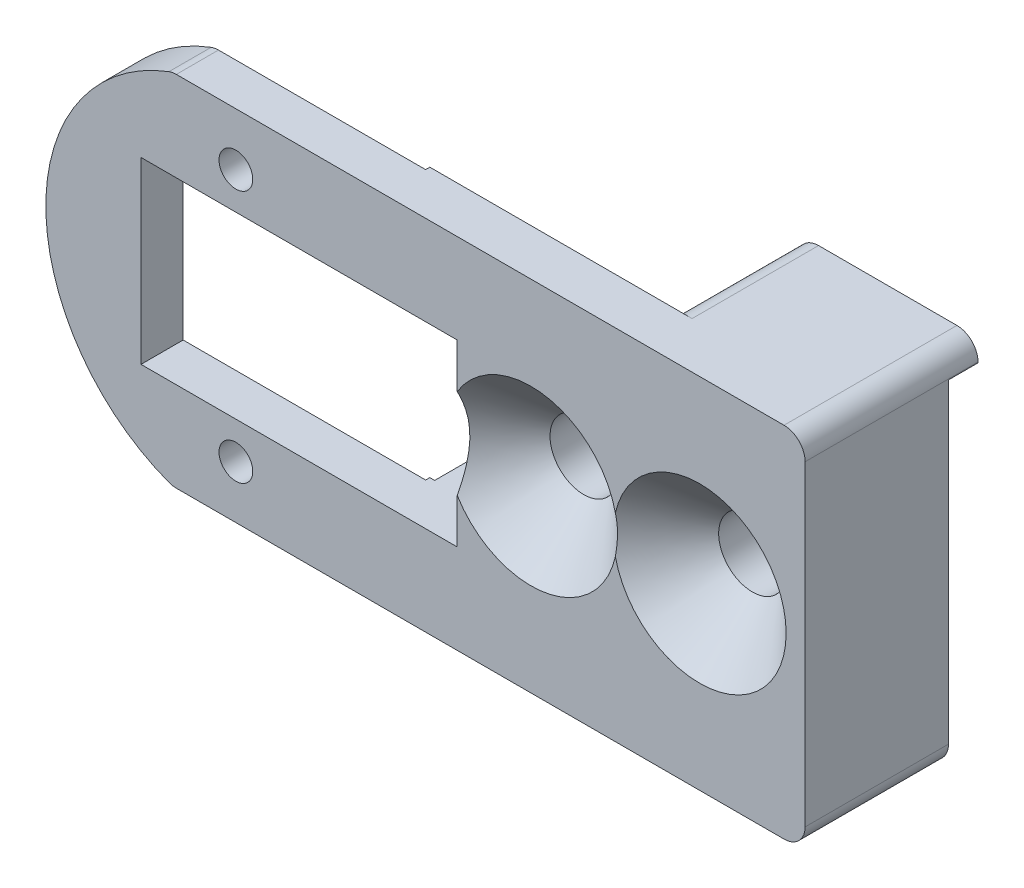
SolidWorks part; units mm, degrees
ref_plane "Front Plane" through (0, 0, 0) normal (0, 0, 1) x (1, 0, 0)
ref_plane "Top Plane" through (0, 0, 0) normal (0, 1, 0) x (1, 0, 0)
ref_plane "Right Plane" through (0, 0, 0) normal (1, 0, 0) x (0, 0, -1)
sketch "Sketch1" plane through (0, 0, 0) normal (0, 0, 1) x (1, 0, 0)
  line L0 (170.9232, 175.5757) -> (267.7046, 169.0678) construction
  line L1 (170.9129, 175.4066) -> (266.125, 169.2097)
  line L2 (268.1688, 170.6248) -> (275.7745, 195.6897)
  line L3 (278.0899, 197.0683) -> (286.8931, 195.2639)
  line L4 (289.2085, 196.6424) -> (291.5751, 204.4416)
  line L5 (289.6612, 207.0223) -> (276.2726, 207.0223)
  line L6 (275.0815, 206.629) -> (256.4226, 192.7962)
  line L7 (255.3092, 192.4043) -> (161.1781, 188.7441)
  line L8 (170.9129, 175.4066) -> (160.0193, 176.7108)
  line L9 (263.8006, 181.4562) -> (263.2585, 179.5311) construction
  line L10 (263.8006, 181.4562) -> (263.2585, 179.5311) construction
  line L11 (264.6293, 181.2229) -> (264.0871, 179.2977) construction
  line L12 (262.972, 181.6896) -> (262.4299, 179.7644) construction
  line L13 (263.2585, 179.5311) -> (263.8006, 181.4562) construction
  line L14 (261.7184, 179.9648) -> (262.2606, 181.8899)
  line L15 (264.7986, 179.0974) -> (265.3407, 181.0225)
  arc A0 (161.1781, 188.7441) -> (160.0193, 176.7108) centre (161.4151, 182.6489) ccw
  arc A1 (255.3092, 192.4043) -> (256.4226, 192.7962) centre (255.2315, 194.4028) ccw
  arc A2 (275.0815, 206.629) -> (276.2726, 207.0223) centre (276.2726, 205.0223) cw
  arc A3 (289.6612, 207.0223) -> (291.5751, 204.4416) centre (289.6612, 205.0223) cw
  arc A4 (289.2085, 196.6424) -> (286.8931, 195.2639) centre (287.2947, 197.2232) cw
  arc A5 (278.0899, 197.0683) -> (275.7745, 195.6897) centre (277.6883, 195.109) ccw
  arc A6 (268.1688, 170.6248) -> (266.125, 169.2097) centre (266.2549, 171.2055) cw
  arc A7 (264.6293, 181.2229) -> (262.972, 181.6896) centre (263.8006, 181.4562) ccw construction
  arc A8 (262.4299, 179.7644) -> (264.0871, 179.2977) centre (263.2585, 179.5311) ccw construction
  arc A9 (261.7184, 179.9648) -> (264.7986, 179.0974) centre (263.2585, 179.5311) ccw
  arc A10 (265.3407, 181.0225) -> (262.2606, 181.8899) centre (263.8006, 181.4562) ccw
  circle A11 centre (287.2947, 201.4292) radius 1.5
  circle A12 centre (161.4151, 182.3428) radius 2
  point P26 (267.7081, 169.1067)
  point P27 (263.5296, 180.4936)
  point P32 (263.5296, 180.4936)
  dimension "D2" = 1.6
  dimension "D1" = 97
sketch "Sketch2" plane through (0, 0, 0) normal (0, 0, 1) x (1, 0, 0)
  line L0 (168.4151, 176.6639) -> (168.4151, 188.0217)
  line L1 (166.4151, 174.8428) -> (166.4151, 189.8428) construction
  line L2 (262.2606, 181.8899) -> (261.7184, 179.9648)
  line L3 (264.7986, 179.0974) -> (265.3407, 181.0225)
  line L4 (262.2606, 181.8899) -> (261.7184, 179.9648)
  line L5 (264.7986, 179.0974) -> (265.3407, 181.0225)
  line L6 (166.4151, 174.8428) -> (156.4151, 174.8428)
  line L7 (156.4151, 174.8428) -> (156.4151, 189.8428) construction
  line L8 (170.9129, 175.4066) -> (266.125, 169.2097)
  line L9 (160.0193, 176.7108) -> (170.9129, 175.4066)
  line L10 (255.3092, 192.4043) -> (161.1781, 188.7441)
  line L11 (275.0815, 206.629) -> (256.4226, 192.7962)
  line L12 (289.6612, 207.0223) -> (276.2726, 207.0223)
  line L13 (289.2085, 196.6424) -> (291.5751, 204.4416)
  line L14 (278.0899, 197.0683) -> (286.8931, 195.2639)
  line L15 (268.1688, 170.6248) -> (275.7745, 195.6897)
  line L16 (170.9129, 175.4066) -> (266.125, 169.2097)
  line L17 (160.0193, 176.7108) -> (170.9129, 175.4066)
  line L18 (255.3092, 192.4043) -> (161.1781, 188.7441)
  line L19 (275.0815, 206.629) -> (256.4226, 192.7962)
  line L20 (289.6612, 207.0223) -> (276.2726, 207.0223)
  line L21 (289.2085, 196.6424) -> (291.5751, 204.4416)
  line L22 (278.0899, 197.0683) -> (286.8931, 195.2639)
  line L23 (268.1688, 170.6248) -> (275.7745, 195.6897)
  line L24 (166.4151, 189.8428) -> (156.4151, 189.8428)
  line L25 (166.4151, 174.8428) -> (156.4151, 189.8428) construction
  line L26 (156.4151, 174.8428) -> (166.4151, 189.8428) construction
  line L27 (161.4151, 174.8428) -> (161.4151, 189.8428) construction
  line L28 (156.4151, 182.3428) -> (166.4151, 182.3428) construction
  circle A0 centre (161.4151, 182.3428) radius 9.0139 construction
  circle A1 centre (287.2947, 201.4292) radius 1.5
  circle A2 centre (287.2947, 201.4292) radius 1.5
  circle A3 centre (161.4151, 182.3428) radius 2
  arc A4 (265.3407, 181.0225) -> (262.2606, 181.8899) centre (263.8006, 181.4562) ccw
  arc A5 (261.7184, 179.9648) -> (264.7986, 179.0974) centre (263.2585, 179.5311) ccw
  arc A6 (265.3407, 181.0225) -> (262.2606, 181.8899) centre (263.8006, 181.4562) ccw
  arc A7 (161.1781, 188.7441) -> (160.0193, 176.7108) centre (161.4151, 182.6489) ccw
  arc A8 (255.3092, 192.4043) -> (256.4226, 192.7962) centre (255.2315, 194.4028) ccw
  arc A9 (276.2726, 207.0223) -> (275.0815, 206.629) centre (276.2726, 205.0223) ccw
  arc A10 (291.5751, 204.4416) -> (289.6612, 207.0223) centre (289.6612, 205.0223) ccw
  arc A11 (286.8931, 195.2639) -> (289.2085, 196.6424) centre (287.2947, 197.2232) ccw
  arc A12 (278.0899, 197.0683) -> (275.7745, 195.6897) centre (277.6883, 195.109) ccw
  arc A13 (266.125, 169.2097) -> (268.1688, 170.6248) centre (266.2549, 171.2055) ccw
  arc A14 (161.1781, 188.7441) -> (160.0193, 176.7108) centre (161.4151, 182.6489) ccw
  arc A15 (255.3092, 192.4043) -> (256.4226, 192.7962) centre (255.2315, 194.4028) ccw
  arc A16 (276.2726, 207.0223) -> (275.0815, 206.629) centre (276.2726, 205.0223) ccw
  arc A17 (291.5751, 204.4416) -> (289.6612, 207.0223) centre (289.6612, 205.0223) ccw
  arc A18 (286.8931, 195.2639) -> (289.2085, 196.6424) centre (287.2947, 197.2232) ccw
  arc A19 (278.0899, 197.0683) -> (275.7745, 195.6897) centre (277.6883, 195.109) ccw
  arc A20 (266.125, 169.2097) -> (268.1688, 170.6248) centre (266.2549, 171.2055) ccw
  arc A21 (261.7184, 179.9648) -> (264.7986, 179.0974) centre (263.2585, 179.5311) ccw
  circle A22 centre (161.4151, 182.3428) radius 2
  circle A23 centre (161.4151, 182.3428) radius 9.0139 construction
  arc A24 (156.4151, 174.8428) -> (156.4151, 189.8428) centre (161.4151, 182.3428) cw
  arc A25 (166.4151, 174.8428) -> (168.4151, 176.6639) centre (161.4151, 182.3428) ccw
  arc A26 (168.4151, 188.0217) -> (166.4151, 189.8428) centre (161.4151, 182.3428) ccw
  circle A27 centre (161.4151, 176.3428) radius 1
  circle A28 centre (161.4151, 188.3428) radius 1
  dimension "D8" = 2
  dimension "D5" = 15
  dimension "D6" = 10
  dimension "D7" = 2
  dimension "D9" = 1.5
  dimension "D1" = 0
  dimension "D2" = 0
  dimension "D3" = 0
  dimension "D4" = 0
sketch "Sketch3" plane through (0, 0, 0) normal (0, 0, 1) x (1, 0, 0)
  line L0 (158.4151, 190.8428) -> (183.4151, 190.8428)
  line L1 (166.4151, 189.8428) -> (156.4151, 189.8428) construction
  line L2 (262.2606, 181.8899) -> (261.7184, 179.9648)
  line L3 (264.7986, 179.0974) -> (265.3407, 181.0225)
  line L4 (262.2606, 181.8899) -> (261.7184, 179.9648) construction
  line L5 (264.7986, 179.0974) -> (265.3407, 181.0225) construction
  line L6 (158.4151, 173.8428) -> (183.4151, 173.8428)
  line L7 (166.4151, 174.8428) -> (156.4151, 174.8428) construction
  line L8 (170.9129, 175.4066) -> (266.125, 169.2097)
  line L9 (160.0193, 176.7108) -> (170.9129, 175.4066)
  line L10 (255.3092, 192.4043) -> (161.1781, 188.7441)
  line L11 (275.0815, 206.629) -> (256.4226, 192.7962)
  line L12 (289.6612, 207.0223) -> (276.2726, 207.0223)
  line L13 (289.2085, 196.6424) -> (291.5751, 204.4416)
  line L14 (278.0899, 197.0683) -> (286.8931, 195.2639)
  line L15 (268.1688, 170.6248) -> (275.7745, 195.6897)
  line L16 (170.9129, 175.4066) -> (266.125, 169.2097) construction
  line L17 (160.0193, 176.7108) -> (170.9129, 175.4066) construction
  line L18 (255.3092, 192.4043) -> (161.1781, 188.7441) construction
  line L19 (275.0815, 206.629) -> (256.4226, 192.7962) construction
  line L20 (289.6612, 207.0223) -> (276.2726, 207.0223) construction
  line L21 (289.2085, 196.6424) -> (291.5751, 204.4416) construction
  line L22 (278.0899, 197.0683) -> (286.8931, 195.2639) construction
  line L23 (268.1688, 170.6248) -> (275.7745, 195.6897) construction
  line L24 (183.4151, 190.8428) -> (183.4151, 173.8428)
  arc A0 (156.4151, 189.8428) -> (156.4151, 174.8428) centre (161.4151, 182.3428) ccw construction
  circle A1 centre (287.2947, 201.4292) radius 1.5
  circle A2 centre (287.2947, 201.4292) radius 1.5 construction
  circle A3 centre (161.4151, 182.3428) radius 2
  arc A4 (265.3407, 181.0225) -> (262.2606, 181.8899) centre (263.8006, 181.4562) ccw
  arc A5 (261.7184, 179.9648) -> (264.7986, 179.0974) centre (263.2585, 179.5311) ccw
  arc A6 (265.3407, 181.0225) -> (262.2606, 181.8899) centre (263.8006, 181.4562) ccw construction
  arc A7 (161.1781, 188.7441) -> (160.0193, 176.7108) centre (161.4151, 182.6489) ccw
  arc A8 (255.3092, 192.4043) -> (256.4226, 192.7962) centre (255.2315, 194.4028) ccw
  arc A9 (276.2726, 207.0223) -> (275.0815, 206.629) centre (276.2726, 205.0223) ccw
  arc A10 (291.5751, 204.4416) -> (289.6612, 207.0223) centre (289.6612, 205.0223) ccw
  arc A11 (286.8931, 195.2639) -> (289.2085, 196.6424) centre (287.2947, 197.2232) ccw
  arc A12 (278.0899, 197.0683) -> (275.7745, 195.6897) centre (277.6883, 195.109) ccw
  arc A13 (266.125, 169.2097) -> (268.1688, 170.6248) centre (266.2549, 171.2055) ccw
  arc A14 (161.1781, 188.7441) -> (160.0193, 176.7108) centre (161.4151, 182.6489) ccw construction
  arc A15 (255.3092, 192.4043) -> (256.4226, 192.7962) centre (255.2315, 194.4028) ccw construction
  arc A16 (276.2726, 207.0223) -> (275.0815, 206.629) centre (276.2726, 205.0223) ccw construction
  arc A17 (291.5751, 204.4416) -> (289.6612, 207.0223) centre (289.6612, 205.0223) ccw construction
  arc A18 (286.8931, 195.2639) -> (289.2085, 196.6424) centre (287.2947, 197.2232) ccw construction
  arc A19 (278.0899, 197.0683) -> (275.7745, 195.6897) centre (277.6883, 195.109) ccw construction
  arc A20 (266.125, 169.2097) -> (268.1688, 170.6248) centre (266.2549, 171.2055) ccw construction
  arc A21 (261.7184, 179.9648) -> (264.7986, 179.0974) centre (263.2585, 179.5311) ccw construction
  circle A22 centre (161.4151, 182.3428) radius 2 construction
  arc A23 (156.4151, 189.8428) -> (156.4151, 174.8428) centre (161.4151, 182.3428) ccw
  circle A24 centre (161.4151, 176.3428) radius 1 construction
  circle A25 centre (161.4151, 188.3428) radius 1 construction
  circle A26 centre (161.4151, 176.3428) radius 1
  circle A27 centre (161.4151, 188.3428) radius 1
  circle A28 centre (161.4151, 182.3428) radius 9.0139 construction
  arc A29 (156.4151, 189.8428) -> (158.4151, 190.8428) centre (161.4151, 182.3428) cw
  arc A30 (156.4151, 174.8428) -> (158.4151, 173.8428) centre (161.4151, 182.3428) ccw
  dimension "D5" = 1
  dimension "D6" = 1
  dimension "D7" = 25
  dimension "D1" = 0
  dimension "D2" = 0
  dimension "D3" = 0
  dimension "D4" = 0
sketch "Sketch4" plane through (0, 0, 0) normal (0, 0, 1) x (1, 0, 0)
  line L0 (158.4151, 173.8428) -> (183.4151, 173.8428) construction
  line L1 (158.4151, 190.8428) -> (183.4151, 190.8428) construction
  line L2 (183.4151, 190.8428) -> (183.4151, 173.8428) construction
  line L3 (158.4151, 173.8428) -> (183.4151, 173.8428) construction
  line L4 (158.4151, 190.8428) -> (183.4151, 190.8428) construction
  line L5 (183.4151, 190.8428) -> (183.4151, 173.8428) construction
  line L6 (170.9129, 175.4066) -> (266.125, 169.2097) construction
  line L7 (255.3092, 192.4043) -> (161.1781, 188.7441) construction
  line L8 (170.9129, 175.4066) -> (266.125, 169.2097) construction
  line L9 (255.3092, 192.4043) -> (161.1781, 188.7441) construction
  line L10 (183.4151, 190.8428) -> (183.4151, 173.8428) construction
  line L11 (183.4151, 173.8428) -> (168.4151, 173.8428)
  line L12 (168.4151, 173.8428) -> (168.4151, 190.8428)
  line L13 (168.4151, 190.8428) -> (183.4151, 190.8428)
  line L14 (183.4151, 182.3428) -> (168.4151, 182.3428) construction
  line L15 (183.4151, 190.8428) -> (188.4151, 190.8428)
  line L16 (188.4151, 190.8428) -> (188.4151, 173.8428)
  line L17 (188.4151, 173.8428) -> (183.4151, 173.8428)
  circle A0 centre (175.4151, 182.3428) radius 1.6
  circle A1 centre (183.4151, 182.3428) radius 1.6
  dimension "D1" = 3.2
  dimension "D2" = 3.2
  dimension "D3" = 5
  dimension "D4" = 7
  dimension "D5" = 15
  dimension "D6" = 5
extrude "Boss-Extrude1" add sketch "Sketch4" along normal blind 4.8
sketch "Sketch5" plane through (0, 0, 4.8) normal (0, 0, 1) x (1, 0, 0)
  line L0 (158.4151, 190.8428) -> (183.4151, 190.8428) construction
  line L1 (158.4151, 190.8428) -> (183.4151, 190.8428)
  line L2 (183.4151, 190.8428) -> (183.4151, 173.8428) construction
  line L3 (158.4151, 173.8428) -> (183.4151, 173.8428) construction
  line L4 (183.4151, 190.8428) -> (183.4151, 173.8428) construction
  line L5 (158.4151, 173.8428) -> (183.4151, 173.8428)
  line L6 (188.4151, 173.8428) -> (188.4151, 190.8428) construction
  line L7 (168.4151, 173.8428) -> (188.4151, 173.8428) construction
  line L8 (188.4151, 190.8428) -> (168.4151, 190.8428) construction
  line L9 (188.4151, 173.8428) -> (188.4151, 190.8428)
  line L10 (168.4151, 173.8428) -> (188.4151, 173.8428)
  line L11 (188.4151, 190.8428) -> (168.4151, 190.8428)
  arc A0 (156.4151, 189.8428) -> (156.4151, 174.8428) centre (161.4151, 182.3428) ccw construction
  arc A1 (156.4151, 189.8428) -> (156.4151, 174.8428) centre (161.4151, 182.3428) ccw
  circle A2 centre (161.4151, 182.3428) radius 9.0139 construction
  circle A3 centre (161.4151, 176.3428) radius 1 construction
  circle A4 centre (161.4151, 188.3428) radius 1 construction
  circle A5 centre (175.4151, 182.3428) radius 1.6 construction
  circle A6 centre (183.4151, 182.3428) radius 1.6 construction
  circle A7 centre (161.4151, 182.3428) radius 9.0139 construction
  circle A8 centre (161.4151, 176.3428) radius 1 construction
  circle A9 centre (161.4151, 188.3428) radius 1 construction
  circle A10 centre (175.4151, 182.3428) radius 1.6
  circle A11 centre (183.4151, 182.3428) radius 1.6
  arc A12 (156.4151, 189.8428) -> (158.4151, 190.8428) centre (161.4151, 182.3428) cw
  arc A13 (156.4151, 174.8428) -> (158.4151, 173.8428) centre (161.4151, 182.3428) ccw
  circle A14 centre (161.4151, 188.3428) radius 0.8
  circle A15 centre (161.4151, 176.3428) radius 0.8
  dimension "D1" = 1.6
  dimension "D2" = 1.6
extrude "Boss-Extrude3" add sketch "Sketch5" along normal blind 2
sketch "Sketch6" plane through (0, 0, 0) normal (0, 0, -1) x (-1, 0, 0)
  line L0 (-183.4151, 190.8428) -> (-183.4151, 189.6088) construction
  line L1 (-255.3092, 192.4043) -> (-161.1781, 188.7441) construction
  line L2 (-183.4151, 190.8428) -> (-183.4151, 173.8428) construction
  line L3 (-183.4151, 189.6088) -> (-168.4151, 189.0256)
  line L4 (-168.4151, 189.0256) -> (-168.4151, 190.8428)
  line L5 (-168.4151, 190.8428) -> (-183.4151, 190.8428)
  line L6 (-168.4151, 190.8428) -> (-168.4151, 173.8428) construction
  line L7 (-183.4151, 190.8428) -> (-188.4151, 190.8428)
  line L8 (-188.4151, 190.8428) -> (-188.4151, 189.8032)
  line L9 (-188.4151, 189.8032) -> (-183.4151, 189.6088)
extrude "Boss-Extrude4" add sketch "Sketch6" along normal blind 1.4
sketch "Sketch8" plane through (0, 0, 0) normal (0, 0, -1) x (-1, 0, 0)
  line L0 (-180.4151, 190.8428) -> (-168.4151, 177.8428)
  line L1 (-158.4151, 190.8428) -> (-183.4151, 190.8428) construction
  line L2 (-168.4151, 176.6639) -> (-168.4151, 188.0217) construction
  line L3 (-168.4151, 177.8428) -> (-168.4151, 190.8428)
  line L4 (-168.4151, 190.8428) -> (-180.4151, 190.8428)
  dimension "D1" = 3
  dimension "D2" = 13
extrude "Cut-Extrude1" cut sketch "Sketch8" against normal blind 4.6 and the other way blind 1.4
chamfer "Chamfer1" distance 2.5 angle 45 2 edges at (185.0151, 182.3428, 6.8) (177.0151, 182.3428, 6.8)
fillet "Fillet1" radius 1 6 edges at (158.4151, 173.8428, 5.8) (158.4151, 190.8428, 5.8) (180.4151, 190.8428, 1.6) (168.4151, 173.8428, 2.4) (188.4151, 173.8428, 3.4) (188.4151, 190.8428, 2.7)
sketch "Sketch9" plane through (0, 0, 6.8) normal (0, 0, 1) x (1, 0, 0)
  line L0 (161.4151, 188.3428) -> (161.4151, 176.3428) construction
  line L1 (165.9151, 186.5928) -> (171.9151, 186.5928)
  line L2 (156.9151, 178.0928) -> (165.9151, 178.0928)
  line L3 (156.9151, 178.0928) -> (156.9151, 186.5928)
  line L4 (156.9151, 186.5928) -> (165.9151, 186.5928)
  line L5 (165.9151, 178.0928) -> (165.9151, 186.5928) construction
  line L6 (156.9151, 178.0928) -> (165.9151, 186.5928) construction
  line L7 (156.9151, 186.5928) -> (165.9151, 178.0928) construction
  line L8 (171.9151, 186.5928) -> (171.9151, 178.0928)
  line L9 (171.9151, 178.0928) -> (165.9151, 178.0928)
  point P4 (161.4151, 182.3428)
  dimension "D1" = 9
  dimension "D2" = 8.5
  dimension "D3" = 6
extrude "Cut-Extrude2" cut sketch "Sketch9" against normal blind 10
